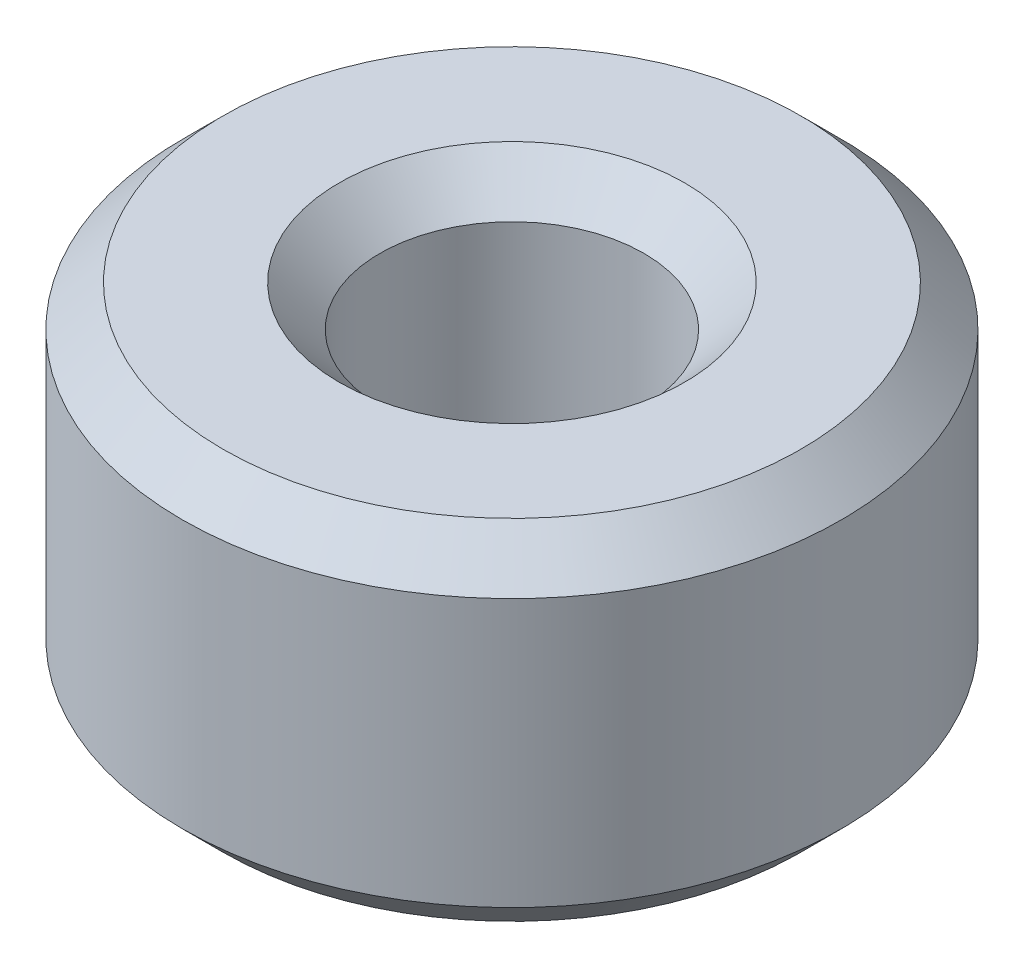
SolidWorks part; units mm, degrees
ref_plane "Front Plane" through (0, 0, 0) normal (0, 0, 1) x (1, 0, 0)
ref_plane "Top Plane" through (0, 0, 0) normal (0, 1, 0) x (1, 0, 0)
ref_plane "Right Plane" through (0, 0, 0) normal (1, 0, 0) x (0, 0, -1)
sketch "Sketch1" plane through (0, 0, 0) normal (0, 1, 0) x (1, 0, 0)
  circle A0 centre (0, 0) radius 17.5
  dimension "SLEEVE_OD" = 35
extrude "Boss-Extrude1" add sketch "Sketch1" along normal blind 18.531
sketch "Sketch2" plane through (0, 0, 0) normal (0, 1, 0) x (1, 0, 0)
  circle A0 centre (0, 0) radius 7.0116
  dimension "BORE_D" = 14.0232
extrude "Cut-Extrude1" cut sketch "Sketch2" along normal through all
chamfer "Chamfer1" distance 2.1617 angle 45 4 edges at (0, 18.531, 7.0116) (0, 0, 7.0116) (0, 0, 17.5) (0, 18.531, 17.5)
